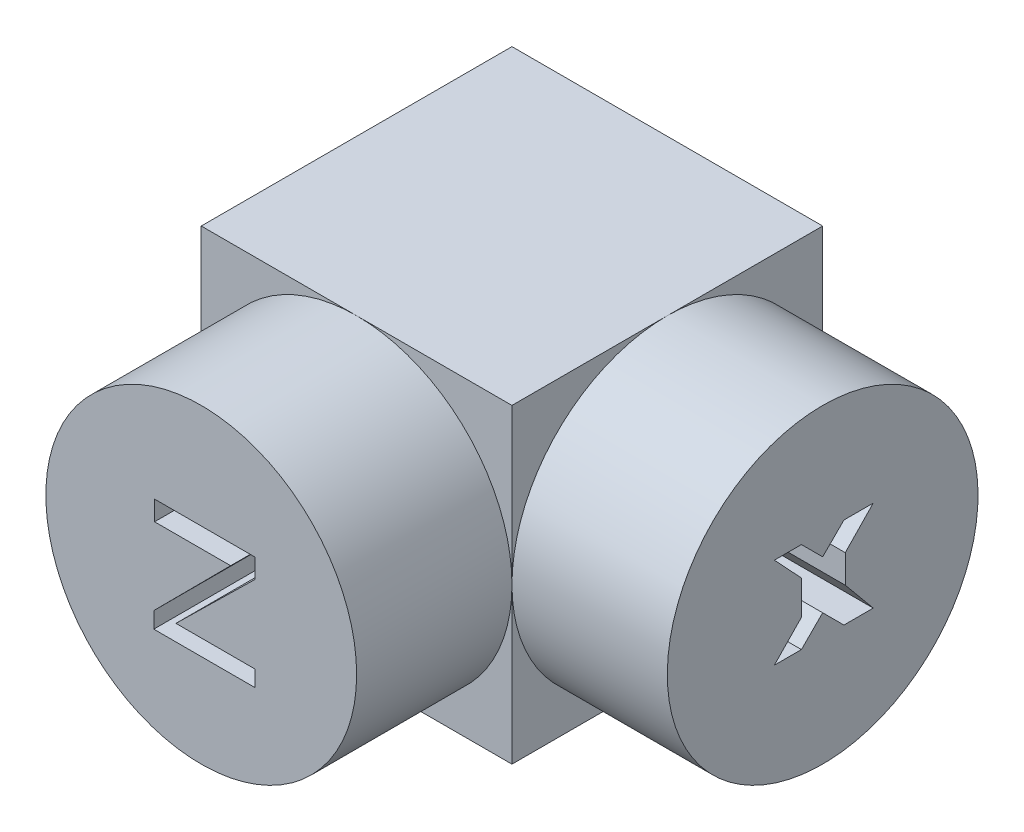
SolidWorks part; units mm, degrees
ref_plane "Front Plane" through (0, 0, 0) normal (0, 0, 1) x (1, 0, 0)
ref_plane "Top Plane" through (0, 0, 0) normal (0, 1, 0) x (1, 0, 0)
ref_plane "Right Plane" through (0, 0, 0) normal (1, 0, 0) x (0, 0, -1)
sketch "Sketch1" plane through (0, 0, 0) normal (0, 0, 1) x (1, 0, 0)
  line L1 (-0.025, 0.025) -> (0.025, 0.025)
  line L2 (-0.025, 0.025) -> (-0.025, -0.025)
  line L3 (-0.025, -0.025) -> (0.025, -0.025)
  line L4 (0.025, 0.025) -> (0.025, -0.025)
  dimension "D1" = 0.025
  dimension "D2" = 0.025
  dimension "D3" = 0.025
  dimension "D4" = 0.025
extrude "Extrude1" add sketch "Sketch1" along normal blind 0.025 and the other way blind 0.025
sketch "Sketch3" plane through (0, 0, 0.025) normal (0, 0, 1) x (1, 0, 0)
  line L0 (-0.0075, 0.0082) -> (0.0086, 0.0082)
  line L1 (0.0086, 0.0082) -> (0.0086, 0.005)
  line L2 (-0.0041, -0.0074) -> (0.0086, -0.0074)
  line L3 (0.0086, -0.0074) -> (0.0086, -0.01)
  line L4 (0.0086, -0.01) -> (-0.0076, -0.01)
  line L5 (-0.0076, -0.01) -> (-0.0076, -0.0074)
  line L6 (-0.0076, -0.0074) -> (0.0047, 0.005)
  line L7 (0.0047, 0.005) -> (-0.0075, 0.005)
  line L8 (-0.0075, 0.005) -> (-0.0075, 0.0082)
  line L9 (0.0086, 0.005) -> (-0.0041, -0.0074)
  circle A0 centre (0, 0) radius 0.025
extrude "Extrude2" add sketch "Sketch3" along normal blind 0.025
sketch "Sketch4" plane through (0.025, 0, 0) normal (1, 0, 0) x (0, 0, -1)
  line L0 (-0.0078, 0.0073) -> (-0.0034, 0.0073)
  line L1 (-0.0034, 0.0073) -> (0, 0.0039)
  line L2 (0, 0.0039) -> (0.0034, 0.0073)
  line L3 (0.0034, 0.0073) -> (0.0081, 0.0073)
  line L4 (0.0081, -0.0073) -> (0.0036, -0.0019)
  line L5 (0.0036, -0.0019) -> (0.0036, 0.0027)
  line L6 (0.0081, -0.0073) -> (0.0034, -0.0073)
  line L7 (0.0034, -0.0073) -> (0, -0.0039)
  line L8 (0, -0.0039) -> (-0.0034, -0.0073)
  line L9 (-0.0034, -0.0073) -> (-0.0078, -0.0073)
  line L10 (0.0036, 0.0027) -> (0.0081, 0.0073)
  line L11 (-0.0078, -0.0073) -> (-0.0034, -0.0028)
  line L12 (-0.0034, -0.0028) -> (-0.0034, 0.0027)
  line L13 (-0.0034, 0.0027) -> (-0.0078, 0.0073)
  circle A0 centre (0, 0) radius 0.025
extrude "Extrude3" add sketch "Sketch4" along normal blind 0.025
